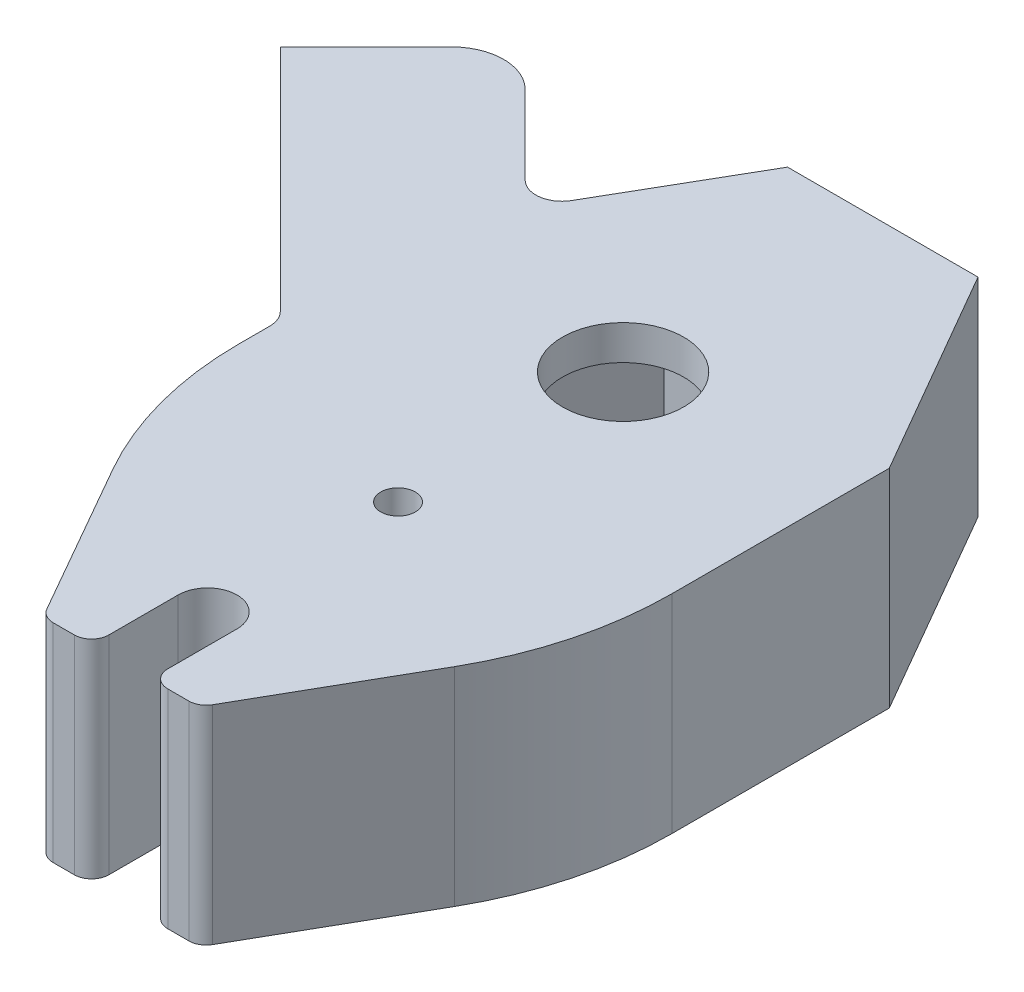
SolidWorks part; units mm, degrees
note: '?' marks a value the reader was unsure of.
ref_plane "Front Plane" through (0, 0, 0) normal (0, 0, 1) x (1, 0, 0)
ref_plane "Top Plane" through (0, 0, 0) normal (0, 1, 0) x (1, 0, 0)
ref_plane "Right Plane" through (0, 0, 0) normal (1, 0, 0) x (0, 0, -1)
ref_axis "Axis1" through (0, 14.8656, 0) along (0, -1, 0)?
sketch "Sketch1" plane through (0, 0, 0) normal (0, 1, 0) x (1, 0, 0)
  line L0 (0, 15) -> (0, -15) construction
  line L5 (-12.5, 15) -> (12.5, 15)
  line L7 (-12.5, 15) -> (-12.5, -15)
  line L10 (-12.5, -15) -> (12.5, -15)
  line L11 (12.5, 15) -> (12.5, -15)
  line L13 (3.2332, -5.6) -> (6.4663, 0)
  line L14 (6.4663, 0) -> (3.2332, 5.6)
  line L15 (3.2332, 5.6) -> (-3.2332, 5.6)
  line L16 (-3.2332, 5.6) -> (-6.4663, 0)
  line L17 (-6.4663, 0) -> (-3.2332, -5.6)
  line L18 (-3.2332, -5.6) -> (3.2332, -5.6)
  circle A0 centre (0, 0) radius 5.6 construction
  dimension "D3" = 15
  dimension "D4" = 11.2
  dimension "D1" = 25
  dimension "D2" = 30
extrude "Boss-Extrude1" add sketch "Sketch1" along normal blind 12
sketch "Sketch8" plane through (0, 0, 0) normal (0, 1, 0) x (1, 0, 0)
  line L0 (-12.5, -15) -> (12.5, -15) construction
  line L1 (-4.5, -15) -> (4.5, -15)
  line L2 (-4.5, -15) -> (-4.5, -29)
  line L3 (-4.5, -29) -> (-1.7, -29)
  line L4 (4.5, -15) -> (4.5, -29)
  line L5 (0, 0) -> (0, -30) construction
  line L6 (-1.7, -24) -> (-1.7, -29)
  line L7 (1.7, -24) -> (1.7, -29)
  line L8 (1.7, -29) -> (4.5, -29)
  arc A0 (1.7, -24) -> (-1.7, -24) centre (0, -24) ccw
  dimension "D2" = 3.4
  dimension "D1" = 24
  dimension "D3" = 5
  dimension "D4" = 9
extrude "Boss-Extrude6" add sketch "Sketch8" along normal up to surface (12 mm away) up to face at (0, 12, 0)
sketch "Sketch9" plane through (0, 12, 0) normal (0, 1, 0) x (1, 0, 0)
  line L27 (-8.1984, 0) -> (-4.0992, -7.1)
  line L28 (-4.0992, -7.1) -> (4.0992, -7.1)
  line L29 (4.0992, -7.1) -> (8.1984, 0)
  line L30 (8.1984, 0) -> (4.0992, 7.1)
  line L31 (4.0992, 7.1) -> (-4.0992, 7.1)
  line L32 (-4.0992, 7.1) -> (-8.1984, 0)
  line L33 (-8.1984, 0) -> (-4.0992, -7.1)
  line L34 (-4.0992, -7.1) -> (4.0992, -7.1)
  line L35 (4.0992, -7.1) -> (8.1984, 0)
  line L36 (8.1984, 0) -> (4.0992, 7.1)
  line L37 (4.0992, 7.1) -> (-4.0992, 7.1)
  line L38 (-4.0992, 7.1) -> (-8.1984, 0)
  circle A0 centre (0, 0) radius 9
  dimension "D2" = 18
  dimension "D1" = 1.5
extrude "Boss-Extrude7" [suppressed] add sketch "Sketch9" along normal blind 2
sketch "Sketch3" plane through (0, 12, 0) normal (0, 1, 0) x (1, 0, 0)
  line L1 (-5.25, -18.5) -> (5.25, -18.5)
  line L2 (-5.25, -18.5) -> (-5.25, -10.5)
  line L3 (-5.25, -10.5) -> (5.25, -10.5)
  line L4 (5.25, -18.5) -> (5.25, -10.5)
  line L5 (0, 0) -> (0, -30) construction
  line L6 (-5.25, -14.5) -> (5.25, -14.5) construction
  circle A0 centre (0, -14.5) radius 1
  dimension "D3" = 2
  dimension "D1" = 8
  dimension "D2" = 10.5
  dimension "D4" = 14.5
extrude "Boss-Extrude3" [suppressed] add sketch "Sketch3" along normal blind 10
sketch "Sketch5" [suppressed] plane through (5.25, 0, 0) normal (1, 0, 0) x (0, 0, -1)
  line L0 (-14.5, 20) -> (-14.5, 10) construction
  line L1 (-18.5, 20) -> (-10.5, 20) construction
  line L4 (-15, 10) -> (15, 10) construction
  circle A0 centre (-14.5, 15) radius 2
  dimension "D1" = 4
extrude "Cut-Extrude1" [suppressed] cut sketch "Sketch5" against normal blind 5
chamfer "Chamfer1" distance 7 angle 60 2 edges at (-12.5, 6, -15) (12.5, 6, -15)
sketch "Sketch6" plane through (0, 0, 0) normal (0, 1, 0) x (1, 0, 0)
  line L0 (0, 0) -> (0, -19.1236) construction
  line L1 (0, 0) -> (-9.432, 9.432) construction
  line L11 (-9.432, 9.432) -> (-19.3315, -0.4675) construction
  line L12 (-26.163, 6.364) -> (-12.5, -7.299)
  line L13 (-26.163, 6.364) -> (-19.0919, 13.435)
  line L14 (-19.0919, 13.435) -> (-11.0478, 5.3909)
  line L18 (-5.5, 15) -> (-12.5, 2.8756) construction
  line L19 (-12.5, 2.8756) -> (-12.5, -15) construction
  line L20 (-12.5, -7.299) -> (-12.5, 2.8756)
  line L21 (-12.5, 2.8756) -> (-11.0478, 5.3909)
  dimension "D1" = 45
  dimension "D3" = 23
  dimension "D4" = 10
  dimension "D5" = 14
extrude "Boss-Extrude4" add sketch "Sketch6" along normal up to surface (12 mm away) up to face at (0, 12, 13.3249)
sketch "Sketch7" plane through (-9.8995, 0, 9.8995) normal (-0.7071, 0, 0.7071) x (0.7071, 0, 0.7071)
  line L0 (-18, 12) -> (-18, 0) construction
  line L1 (-3.6777, 12) -> (-23, 12) construction
  line L2 (-3.6777, 0) -> (-23, 0) construction
  line L3 (-23, 12) -> (-23, 0) construction
  circle A0 centre (-18, 6) radius 2.8
  dimension "D1" = 5.6
  dimension "D2" = 5
extrude "Cut-Extrude2" cut sketch "Sketch7" against normal blind 12
chamfer "Chamfer2" distance 14 distance2 8 1 edges at (4.5, 6, 15)
chamfer "Chamfer3" distance 8 distance2 14 1 edges at (-4.5, 6, 15)
fillet "Fillet2" radius 20 2 edges at (-12.5, 6, 15) (12.5, 6, 15)
fillet "Fillet3" radius 1 4 edges at (1.7, 6, 29) (-1.7, 6, 29) (4.5, 6, 29) (-4.5, 6, 29)
draft "Draft1" [suppressed] type of draft neutral plane draft angle 10 faces to draft 2 parameters "D1"=10
draft "Draft2" [suppressed] type of draft neutral plane draft angle 5 faces to draft 7 parameters "D1"=5
fillet "Fillet4" radius 1.5 2 edges at (-11.0478, 6, -5.3909) (-12.5, 6, 7.299)
sketch "Sketch10" plane through (0, 12, 0) normal (0, 1, 0) x (1, 0, 0)
  circle A0 centre (0, -13) radius 1
  dimension "D2" = 2
  dimension "D1" = 13
extrude "Cut-Extrude3" cut sketch "Sketch10" against normal through all
sketch "Sketch11" plane through (0, 0, 0) normal (1, 0, 0) x (0, 0, -1)
  line L0 (-12, 12) -> (-14, 12) construction
  line L1 (-12, 12) -> (-14, 12) construction
  line L2 (-14, 0) -> (-12, 0) construction
  line L3 (-14, 0) -> (-12, 0) construction
  line L4 (-13, 12) -> (-13, 0) construction
  circle A0 centre (-13, 6) radius 2
  dimension "D1" = 4
extrude "Cut-Extrude4" cut sketch "Sketch11" against normal through all
sketch "Sketch12" plane through (0, 12, 0) normal (0, 1, 0) x (1, 0, 0)
  line L0 (3.2332, 5.6) -> (-3.2332, 5.6) construction
  line L1 (6.4663, 0) -> (3.2332, 5.6) construction
  line L2 (3.2332, -5.6) -> (6.4663, 0) construction
  line L3 (-3.2332, -5.6) -> (3.2332, -5.6) construction
  line L4 (-6.4663, 0) -> (-3.2332, -5.6) construction
  line L5 (-3.2332, 5.6) -> (-6.4663, 0) construction
  line L6 (3.2332, 5.6) -> (-3.2332, 5.6)
  line L7 (6.4663, 0) -> (3.2332, 5.6)
  line L8 (3.2332, -5.6) -> (6.4663, 0)
  line L9 (-3.2332, -5.6) -> (3.2332, -5.6)
  line L10 (-6.4663, 0) -> (-3.2332, -5.6)
  line L11 (-3.2332, 5.6) -> (-6.4663, 0)
  circle A0 centre (0, 0) radius 3.5
  dimension "D1" = 7
extrude "Boss-Extrude8" add sketch "Sketch12" against normal offset from surface (2 mm away) 10 up to face at (0, 0, 14)
sketch "Sketch13" plane through (-12.5, 0, 0) normal (1, 0, 0) x (0, 0, -1)
  circle A0 centre (-13, 6) radius 3.5
  dimension "D1" = 7
extrude "Cut-Extrude5" [suppressed] cut sketch "Sketch13" along normal blind 8
fillet "Fillet5" radius 3 1 edges at (-19.0919, 6, -13.435)
